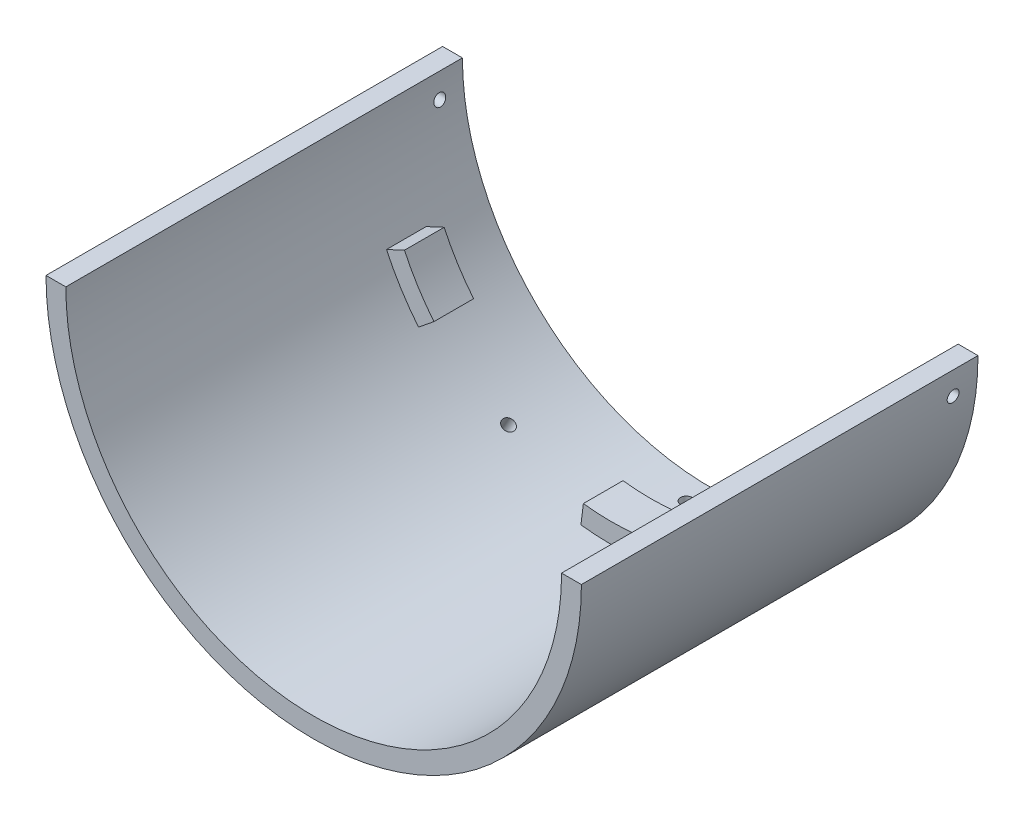
SolidWorks part; units mm, degrees
ref_plane "Front Plane" through (0, 0, 0) normal (0, 0, 1) x (1, 0, 0)
ref_plane "Top Plane" through (0, 0, 0) normal (0, 1, 0) x (1, 0, 0)
ref_plane "Right Plane" through (0, 0, 0) normal (1, 0, 0) x (0, 0, -1)
sketch "Sketch1" plane through (0, 0, 0) normal (0, 0, 1) x (1, 0, 0)
  line L0 (-62.5, 0) -> (-67.5, 0)
  line L1 (62.5, 0) -> (67.5, 0)
  circle A0 centre (0, 0) radius 62.5
  circle A1 centre (0, 0) radius 67.5
  dimension "D1" = 125
  dimension "D2" = 5
extrude "Boss-Extrude1" add sketch "Sketch1" along normal blind 100 contours L0 A1 L1 A0 region at (0, -64.0093, 0)
ref_plane "Plane1" through (0, 0, 15) normal (0, 0, 1) x (1, 0, 0)
sketch "Sketch3" plane through (0, 0, 15) normal (0, 0, 1) x (1, 0, 0)
  line L0 (-56.6442, -26.4136) -> (-52.1127, -24.3006)
  line L1 (-48.5716, -39.3325) -> (-44.6859, -36.1859)
  line L3 (52.1127, -24.3006) -> (56.6442, -26.4136)
  line L4 (44.6859, -36.1859) -> (48.5716, -39.3325)
  line L7 (7.0075, -57.0714) -> (7.6168, -62.0341)
  line L8 (-7.0075, -57.0714) -> (-7.6168, -62.0341)
  circle A0 centre (0, 0) radius 57.5
  circle A1 centre (0, 0) radius 62.5
  dimension "D1" = 115
  dimension "D2" = 5
  dimension "D3" = 14
  dimension "D5" = 14
  dimension "D8" = 14
extrude "Boss-Extrude3" add sketch "Sketch3" along normal blind 10 contours L0 A1 L1 A0 | L8 A1 L7 A0 | L4 A1 L3 A0 region at (-50.7858, -31.7345, 15) region at (50.7858, -31.7345, 15) region at (0, -59.8855, 15)
ref_plane "Plane2" through (62.5, 0, 0) normal (-1, 0, 0) x (0, 0, 1)
sketch "Sketch4" plane through (62.5, 0, 0) normal (-1, 0, 0) x (0, 0, 1)
  line L0 (100, 0) -> (0, 0) construction
  line L1 (0, 0) -> (0, -67.5) construction
  circle A0 centre (6, -6) radius 1.5
  dimension "D1" = 3
  dimension "D2" = 6
  dimension "D3" = 6
extrude "Cut-Extrude1" cut sketch "Sketch4" against normal blind 16 and the other way blind 149
ref_plane "Plane3" through (0, -62.5, 0) normal (0, 1, 0) x (1, 0, 0)
sketch "Sketch5" plane through (0, -62.5, 0) normal (0, 1, 0) x (1, 0, 0)
  line L0 (0, -37.125) -> (0, 37.125) construction
  line L1 (-37.125, 0) -> (37.125, 0) construction
  circle A0 centre (0, -6) radius 1.5
  dimension "D1" = 3
  dimension "D2" = 6
extrude "Cut-Extrude2" cut sketch "Sketch5" against normal blind 16 and the other way blind 16
ref_plane "Plane4" through (0, 0, 0) normal (0.8746, -0.4848, 0) x (0, 0, -1)
ref_plane "Plane5" through (-30.3006, -54.6637, 0) normal (0.4848, 0.8746, 0) x (0.8746, -0.4848, 0)
sketch "Sketch6" plane through (-30.3006, -54.6637, 0) normal (0.4848, 0.8746, 0) x (0.8746, -0.4848, 0)
  line L2 (-54.6637, -100) -> (-54.6637, 0) construction
  line L3 (-37.125, 0) -> (37.125, 0) construction
  circle A0 centre (-0.6637, -20) radius 1.5
  dimension "D1" = 54
  dimension "D2" = 20
  dimension "D3" = 3
extrude "Cut-Extrude3" cut sketch "Sketch6" against normal blind 16 and the other way blind 16
ref_plane "Plane6" through (0, 0, 0) normal (0.8746, 0.4848, 0) x (0, 0, -1)
ref_plane "Plane7" through (30.3006, -54.6637, 0) normal (-0.4848, 0.8746, 0) x (0.8746, 0.4848, 0)
sketch "Sketch7" plane through (30.3006, -54.6637, 0) normal (-0.4848, 0.8746, 0) x (0.8746, 0.4848, 0)
  line L0 (54.6637, 0) -> (-62.5, 0) construction
  line L1 (54.6637, -100) -> (54.6637, 0) construction
  circle A0 centre (0.6637, -20) radius 1.5
  dimension "D1" = 20
  dimension "D2" = 54
  dimension "D3" = 3
extrude "Cut-Extrude4" cut sketch "Sketch7" against normal blind 16 and the other way blind 16
